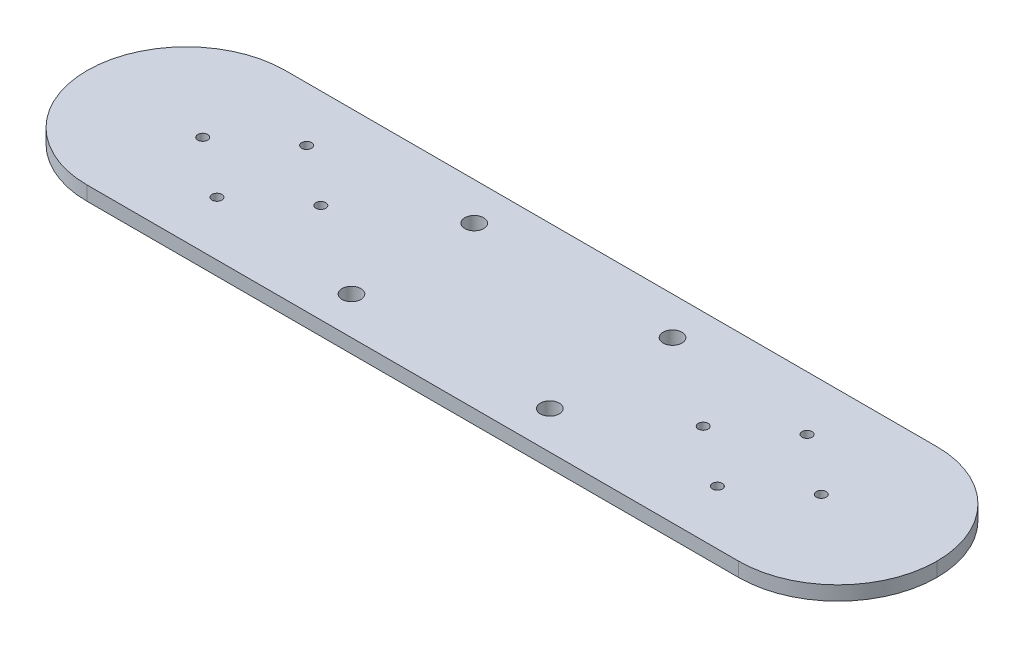
SolidWorks part; units mm, degrees
ref_plane "前视基准面" through (0, 0, 0) normal (0, 0, 1) x (1, 0, 0)
ref_plane "上视基准面" through (0, 0, 0) normal (0, 1, 0) x (1, 0, 0)
ref_plane "右视基准面" through (0, 0, 0) normal (1, 0, 0) x (0, 0, -1)
sketch "草图1" plane through (0, 0, 0) normal (0, 0, 1) x (1, 0, 0)
  line L1 (-90, -1.5) -> (90, -1.5)
  line L2 (-90, -1.5) -> (-90, 1.5)
  line L3 (-90, 1.5) -> (90, 1.5)
  line L4 (90, -1.5) -> (90, 1.5)
  line L5 (-90, -1.5) -> (90, 1.5) construction
  line L6 (-90, 1.5) -> (90, -1.5) construction
  point P0 (0, 0)
  dimension "D1" = 3
  dimension "D2" = 180
extrude "凸台-拉伸1" add sketch "草图1" along normal mid plane 42
sketch "草图2" plane through (0, 1.5, 0) normal (0, 1, 0) x (1, 0, 0)
  line L0 (-21, 13) -> (21, 13) construction
  line L1 (21, 13) -> (21, -13) construction
  line L2 (21, -13) -> (-21, -13) construction
  line L3 (-21, -13) -> (-21, 13) construction
  circle A0 centre (-21, 13) radius 2
  circle A1 centre (21, 13) radius 2
  circle A2 centre (21, -13) radius 2
  circle A3 centre (-21, -13) radius 2
  point P8 (21, 0)
  point P9 (0, 13)
  dimension "D1" = 4
  dimension "D2" = 42
  dimension "D3" = 26
extrude "切除-拉伸1" cut sketch "草图2" against normal through all
sketch "草图3" plane through (0, 1.5, 0) normal (0, 1, 0) x (1, 0, 0)
  circle A0 centre (53, 0) radius 9.5 construction
  circle A1 centre (53, 0) radius 12.5 construction
  circle A2 centre (53, 9.5) radius 1.05
  circle A3 centre (53, -9.5) radius 1.05
  circle A4 centre (40.5, 0) radius 1.05
  circle A5 centre (65.5, 0) radius 1.05
  dimension "D1" = 25
  dimension "D2" = 19
  dimension "D4" = 2.1
  dimension "D3" = 53
extrude "切除-拉伸2" cut sketch "草图3" against normal through all
mirror "镜向1" about plane through (0, 0, 0) normal (1, 0, 0) of "切除-拉伸2"
fillet "圆角1" radius 21 4 edges at (90, 0, 21) (-90, 0, 21) (-90, 0, -21) (90, 0, -21)
